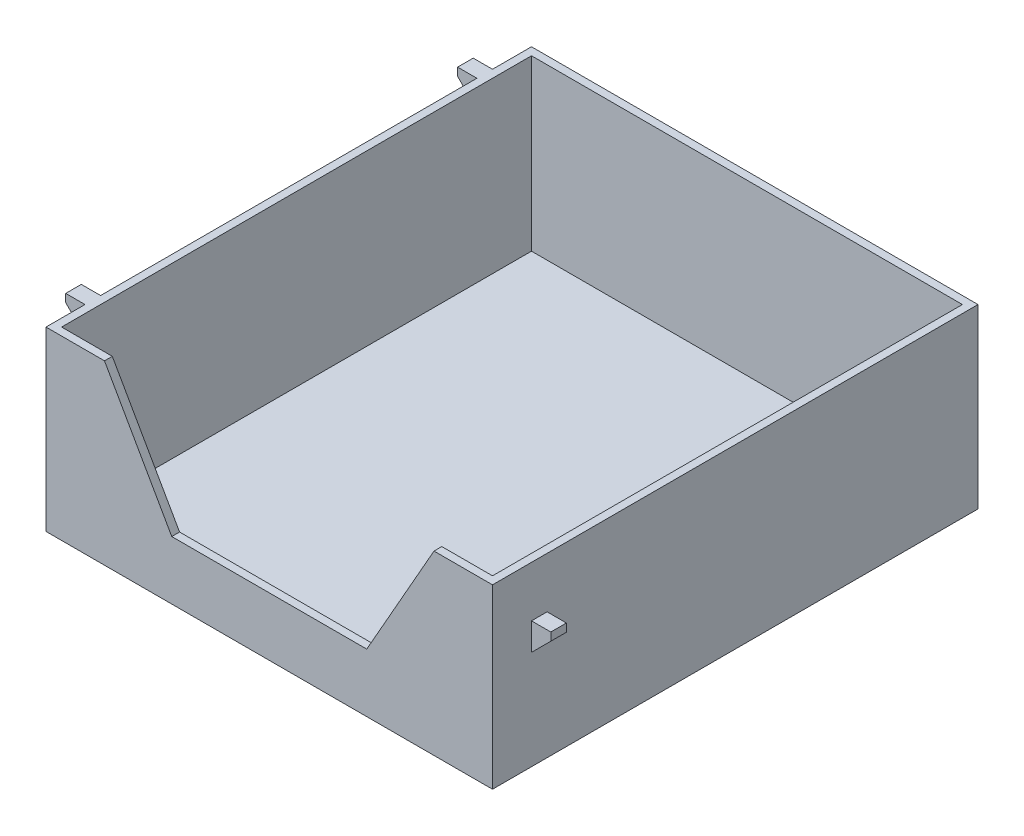
SolidWorks part; units mm, degrees
ref_plane "Plano frontal" through (0, 0, 0) normal (0, 0, 1) x (1, 0, 0)
ref_plane "Plano superior" through (0, 0, 0) normal (0, 1, 0) x (1, 0, 0)
ref_plane "Plano direito" through (0, 0, 0) normal (1, 0, 0) x (0, 0, -1)
sketch "Esboço1" plane through (0, 0, 0) normal (0, 1, 0) x (1, 0, 0)
  line L1 (-57.25, -62.25) -> (57.25, -62.25)
  line L2 (-57.25, -62.25) -> (-57.25, 62.25)
  line L3 (-57.25, 62.25) -> (57.25, 62.25)
  line L4 (57.25, -62.25) -> (57.25, 62.25)
  line L5 (-57.25, -62.25) -> (57.25, 62.25) construction
  line L6 (-57.25, 62.25) -> (57.25, -62.25) construction
  point P0 (0, 0)
  dimension "D1" = 114.5
  dimension "D2" = 124.5
extrude "Ressalto-extrusão1" add sketch "Esboço1" along normal blind 2
sketch "Esboço2" plane through (0, 0, -62.25) normal (0, 0, -1) x (-1, 0, 0)
  line L9 (-57.25, 0) -> (57.25, 0)
  line L10 (-57.25, 0) -> (-57.25, 45.4)
  line L11 (-57.25, 45.4) -> (57.25, 45.4)
  line L12 (57.25, 0) -> (57.25, 45.4)
  dimension "D1" = 45.4
extrude "Ressalto-extrusão2" add sketch "Esboço2" against normal blind 2
sketch "Esboço3" plane through (0, 0, 62.25) normal (0, 0, 1) x (1, 0, 0)
  line L2 (-57.25, 45.4) -> (57.25, 45.4) construction
  line L3 (-42.25, 45.4) -> (-25, 15)
  line L4 (-25, 15) -> (25, 15)
  line L5 (25, 15) -> (42.25, 45.4)
  line L6 (42.25, 45.4) -> (57.25, 45.4)
  line L7 (57.25, 45.4) -> (57.25, 0)
  line L8 (57.25, 0) -> (-57.25, 0)
  line L9 (-42.25, 45.4) -> (-57.25, 45.4)
  line L10 (-57.25, 45.4) -> (-57.25, 0)
  point P4 (0, 15)
  dimension "D1" = 15
  dimension "D2" = 50
  dimension "D3" = 15
extrude "Ressalto-extrusão3" add sketch "Esboço3" against normal blind 2
sketch "Esboço4" plane through (-57.25, 0, 0) normal (-1, 0, 0) x (0, 0, 1)
  line L5 (-62.25, 0) -> (62.25, 0)
  line L6 (-62.25, 0) -> (-62.25, 45.4)
  line L7 (-62.25, 45.4) -> (62.25, 45.4)
  line L8 (62.25, 0) -> (62.25, 45.4)
extrude "Ressalto-extrusão4" add sketch "Esboço4" against normal blind 2
sketch "Esboço5" plane through (57.25, 0, 0) normal (1, 0, 0) x (0, 0, -1)
  line L1 (-62.25, 0) -> (62.25, 0)
  line L2 (-62.25, 0) -> (-62.25, 45.4)
  line L3 (-62.25, 45.4) -> (62.25, 45.4)
  line L4 (62.25, 0) -> (62.25, 45.4)
extrude "Ressalto-extrusão5" add sketch "Esboço5" against normal blind 2
sketch "Esboço6" plane through (0, 0, 62.25) normal (0, 0, 1) x (1, 0, 0)
  line L5 (57.25, 25.4) -> (62.1997, 30.3497)
  line L7 (57.25, 45.4) -> (57.25, 0) construction
  line L8 (62.1997, 30.3497) -> (62.1997, 32.4)
  line L9 (62.1997, 32.4) -> (57.25, 32.4)
  line L10 (57.25, 32.4) -> (57.25, 25.4)
  line L11 (-57.25, 0) -> (57.25, 0) construction
  dimension "D1" = 25.4
  dimension "D2" = 45
  dimension "D3" = 7
  dimension "D4" = 7
extrude "Ressalto-extrusão6" add sketch "Esboço6" against normal blind 4 from offset 10 offset against normal yes
sketch "Esboço8" plane through (0, 0, 62.25) normal (0, 0, 1) x (1, 0, 0)
  line L0 (-57.25, 38.4) -> (-62.1997, 43.3497)
  line L1 (-57.25, 45.4) -> (-57.25, 0) construction
  line L2 (-62.1997, 43.3497) -> (-62.1997, 45.4)
  line L3 (-62.1997, 45.4) -> (-57.25, 45.4)
  line L4 (-57.25, 45.4) -> (-57.25, 38.4)
  line L5 (-57.25, 0) -> (57.25, 0) construction
  dimension "D1" = 38.4
  dimension "D2" = 45
  dimension "D3" = 7
  dimension "D4" = 7
extrude "Ressalto-extrusão7" add sketch "Esboço8" against normal blind 4 from offset 10 offset against normal yes
sketch "Esboço10" plane through (0, 0, -62.25) normal (0, 0, -1) x (-1, 0, 0)
  line L4 (57.25, 45.4) -> (57.25, 38.4)
  line L5 (57.25, 38.4) -> (62.1997, 43.3497)
  line L6 (62.1997, 43.3497) -> (62.1997, 45.4)
  line L7 (62.1997, 45.4) -> (57.25, 45.4)
  line L8 (57.25, 45.4) -> (57.25, 38.4)
  line L9 (57.25, 38.4) -> (62.1997, 43.3497)
  line L10 (62.1997, 43.3497) -> (62.1997, 45.4)
  line L11 (62.1997, 45.4) -> (57.25, 45.4)
  dimension "D1" = 0
extrude "Ressalto-extrusão8" add sketch "Esboço10" against normal blind 4 from offset 10 offset against normal yes
